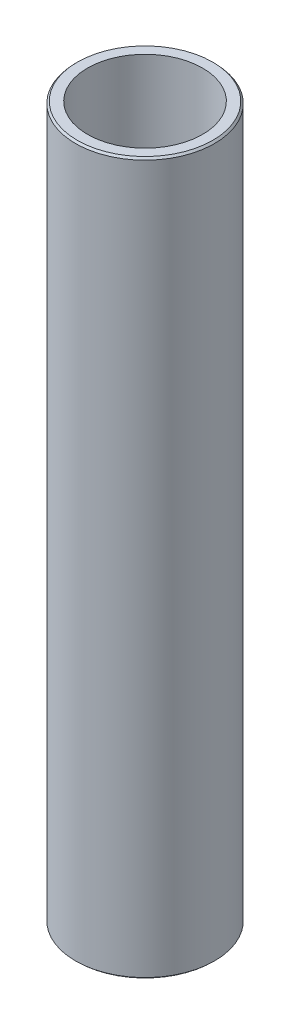
SolidWorks part; units mm, degrees
ref_plane "Front Plane" through (0, 0, 0) normal (0, 0, 1) x (1, 0, 0)
ref_plane "Top Plane" through (0, 0, 0) normal (0, 1, 0) x (1, 0, 0)
ref_plane "Right Plane" through (0, 0, 0) normal (1, 0, 0) x (0, 0, -1)
sketch "Sketch1" plane through (0, 0, 0) normal (0, 1, 0) x (1, 0, 0)
  circle A0 centre (0, 0) radius 55
  dimension "SHAFT_OD" = 110
extrude "Boss-Extrude1" add sketch "Sketch1" along normal blind 563.0647
sketch "Sketch2" plane through (0, 0, 0) normal (0, 1, 0) x (1, 0, 0)
  circle A0 centre (0, 0) radius 45.5245
  dimension "BORE_D" = 91.0491
extrude "Cut-Extrude1" cut sketch "Sketch2" along normal through all
chamfer "Chamfer1" distance 1.5303 angle 42.158 2 edges at (0, 563.0647, 55) (0, 0, 55) first distance on face at (0, 563.0647, 55) first distance on face at (0, 0, 45.5245)
